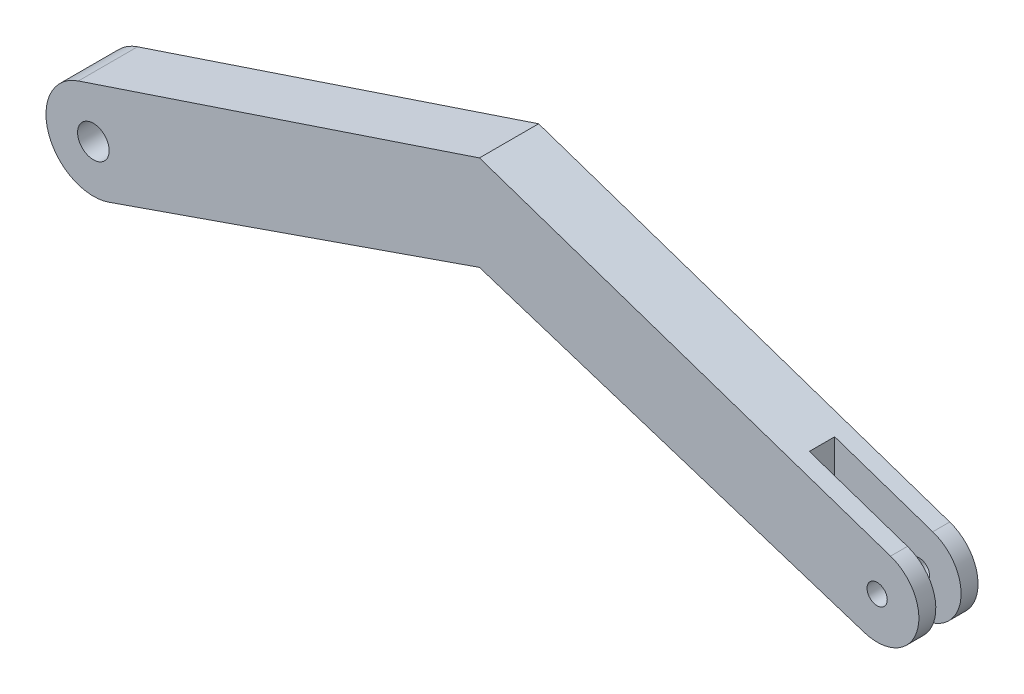
SolidWorks part; units mm, degrees
ref_plane "Front Plane" through (0, 0, 0) normal (0, 0, 1) x (1, 0, 0)
ref_plane "Top Plane" through (0, 0, 0) normal (0, 1, 0) x (1, 0, 0)
ref_plane "Right Plane" through (0, 0, 0) normal (1, 0, 0) x (0, 0, -1)
sketch "Sketch1" plane through (0, 0, 0) normal (0, 0, 1) x (1, 0, 0)
  line L2 (-38.5881, -2.2492) -> (-19.9775, 4.2208)
  line L3 (-19.9775, 4.2208) -> (-0.6413, -1.995)
  line L4 (-40.1239, 2.2587) -> (-19.9775, 8.9833)
  line L5 (-19.9775, 8.9833) -> (0.6726, 1.9846)
  circle A0 centre (0, 0) radius 0.508
  circle A1 centre (-39.37, 0) radius 0.7937
  arc A4 (-40.1239, 2.2587) -> (-38.5881, -2.2492) centre (-39.37, 0) ccw
  arc A5 (-0.6413, -1.995) -> (0.6726, 1.9846) centre (0, 0) ccw
  circle A7 centre (-39.37, 0) radius 2.3813 construction
  circle A8 centre (0, 0) radius 2.0955 construction
  point P6 (-39.37, 0)
  point P7 (2.0955, 0)
  point P8 (0, 0)
  point P9 (2.0955, 0)
  point P13 (-29.7511, 0)
  point P16 (-36.9888, 0)
  dimension "D1" = 1.5875
  dimension "D2" = 1.016
  dimension "D3" = 39.37
  dimension "D5" = 4.7625
  dimension "D4" = 1.5875
extrude "Boss-Extrude1" add sketch "Sketch1" along normal blind 2.9718 contours A0 A1 | A0 region at (-41.1953, -0.6219, 0) region at (0, 0, 0)
sketch "Sketch2" plane through (0, 0, 0) normal (0, 1, 0) x (1, 0, 0)
  line L0 (-25.5731, 0) -> (-25.5731, -2.9718) construction
  line L1 (-4.2545, -2.1209) -> (4.3061, -2.1209)
  line L2 (-4.2545, -2.1209) -> (-4.2545, -0.8509)
  line L3 (-4.2545, -0.8509) -> (4.3061, -0.8509)
  line L4 (4.3061, -2.1209) -> (4.3061, -0.8509)
  line L5 (-4.2545, -2.1209) -> (4.3061, -0.8509) construction
  line L6 (-4.2545, -0.8509) -> (4.3061, -2.1209) construction
  line L8 (0.0258, -2.9718) -> (0.0258, 0) construction
  line L9 (0.0258, 0) -> (0.0258, -2.9718) construction
  line L10 (2.0955, -2.9718) -> (2.0955, 0) construction
  point P0 (-25.5731, -1.4859)
  point P7 (0.0258, -0.8509)
  point P14 (0.0258, -1.4859)
  point P15 (0.0258, -1.4859)
  dimension "D1" = 1.27
  dimension "D2" = 6.35
extrude "Cut-Extrude1" cut sketch "Sketch2" against normal through all both and the other way through all
extrude "Cut-Extrude3" cut sketch "Sketch1<4>" along normal through all both contours A0
sketch "Sketch1<4>" plane through (0, 0, 0) normal (0, 0, 1) x (1, 0, 0) same geometry as "Sketch1"
